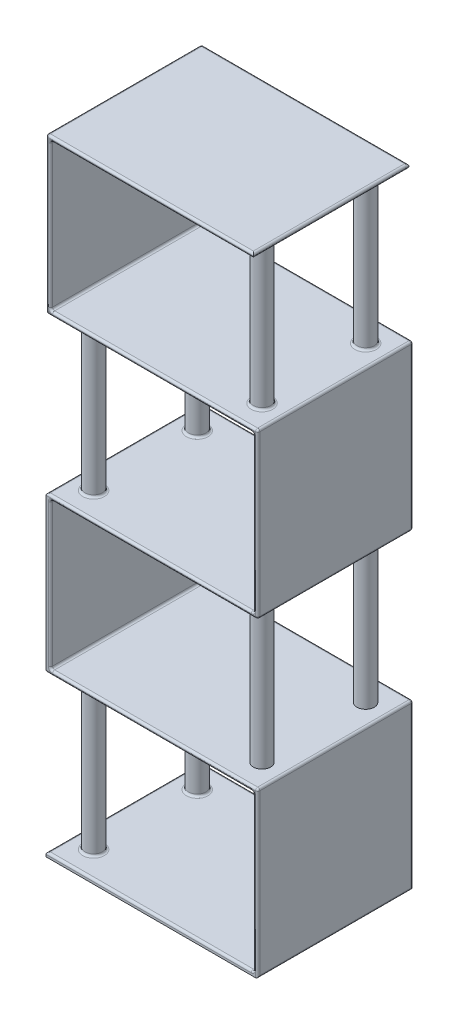
SolidWorks part; units mm, degrees
ref_plane "Front Plane" through (0, 0, 0) normal (0, 0, 1) x (1, 0, 0)
ref_plane "Top Plane" through (0, 0, 0) normal (0, 1, 0) x (1, 0, 0)
ref_plane "Right Plane" through (0, 0, 0) normal (1, 0, 0) x (0, 0, -1)
sketch "Sketch1" plane through (0, 0, 0) normal (0, 0, 1) x (1, 0, 0)
  line L0 (0, 0) -> (609.6, 0)
  line L1 (609.6, 0) -> (609.6, 457.2)
  line L2 (609.6, 457.2) -> (0, 457.2)
  line L3 (0, 457.2) -> (0, 914.4)
  line L4 (0, 914.4) -> (609.6, 914.4)
  line L5 (609.6, 914.4) -> (609.6, 1371.6)
  line L6 (609.6, 1371.6) -> (0, 1371.6)
  line L7 (0, 1371.6) -> (0, 1828.8)
  line L8 (0, 1828.8) -> (609.6, 1828.8)
  line L9 (0, -12.7) -> (622.3, -12.7)
  line L10 (622.3, -12.7) -> (622.3, 469.9)
  line L11 (622.3, 469.9) -> (12.7, 469.9)
  line L12 (12.7, 469.9) -> (12.7, 901.7)
  line L13 (12.7, 901.7) -> (622.3, 901.7)
  line L14 (622.3, 901.7) -> (622.3, 1384.3)
  line L15 (622.3, 1384.3) -> (12.7, 1384.3)
  line L16 (12.7, 1384.3) -> (12.7, 1816.1)
  line L17 (12.7, 1816.1) -> (609.6, 1816.1)
  line L18 (609.6, 1816.1) -> (609.6, 1828.8)
  line L19 (0, -12.7) -> (0, 0)
  dimension "D1" = 609.6
  dimension "D2" = 1828.8
  dimension "D3" = 12.7
extrude "Boss-Extrude1" add sketch "Sketch1" along normal mid plane 457.2
sketch "Sketch2" plane through (0, 0, 0) normal (0, 1, 0) x (1, 0, 0)
  line L0 (0, -228.6) -> (0, 228.6) construction
  circle A0 centre (63.5, 152.4) radius 25.4
  circle A1 centre (63.5, -152.4) radius 25.4
  point P4 (0, 0)
  dimension "D1" = 152.4
  dimension "D4" = 50.8
  dimension "D2" = 152.4
  dimension "D3" = 63.5
extrude "Boss-Extrude2" add sketch "Sketch2" along normal up to next
pattern_linear "LPattern1" count 2 spacing 914.4 along (0, 1, 0) of "Boss-Extrude2"
sketch "Sketch3" plane through (0, 469.9, 0) normal (0, 1, 0) x (1, 0, 0)
  line L0 (622.3, -228.6) -> (622.3, 228.6) construction
  circle A0 centre (558.8, 152.4) radius 25.4
  circle A1 centre (558.8, -152.4) radius 25.4
  point P4 (0, 0)
  dimension "D1" = 152.4
  dimension "D4" = 50.8
  dimension "D2" = 152.4
  dimension "D3" = 63.5
extrude "Boss-Extrude3" add sketch "Sketch3" along normal up to next
pattern_linear "LPattern2" count 2 spacing 914.4 along (0, 1, 0) of "Boss-Extrude3"
fillet "Fillet1" radius 6.35 65 edges at (609.6, 228.6, 228.6) (609.6, 228.6, -228.6) (317.5, 469.9, 228.6) (317.5, 469.9, -228.6) (609.6, 1143, 228.6) (609.6, 1143, -228.6) (12.7, 1600.2, 228.6) (12.7, 1600.2, -228.6) (622.3, -12.7, 0) (622.3, 228.6, 228.6) (622.3, 469.9, 0) (622.3, 228.6, -228.6) (609.6, 0, 0) (304.8, 0, 228.6) (0, 0, 0) (304.8, 0, -228.6) (63.5, 0, -177.8) (63.5, 0, 127) (0, 457.2, 0) (304.8, 457.2, 228.6) (609.6, 457.2, 0) (304.8, 457.2, -228.6) (38.1, 457.2, -152.4) (38.1, 457.2, 152.4) (12.7, 469.9, 0) (12.7, 685.8, 228.6) (12.7, 685.8, -228.6) (12.7, 901.7, 0) (317.5, 901.7, 228.6) (317.5, 901.7, -228.6) (558.8, 901.7, -127) (558.8, 901.7, 177.8) (304.8, 1371.6, 228.6) (609.6, 1371.6, 0) (304.8, 1371.6, -228.6) (38.1, 1371.6, -152.4) (38.1, 1371.6, 152.4) (0, 1600.2, 228.6) (0, 1371.6, 0) (0, 1600.2, -228.6) (622.3, 901.7, 0) (622.3, 1143, 228.6) (622.3, 1143, -228.6) (609.6, 914.4, 0) (304.8, 914.4, 228.6) (0, 914.4, 0) (304.8, 914.4, -228.6) (63.5, 914.4, -177.8) (63.5, 914.4, 127) (622.3, 1384.3, 0) (317.5, 1384.3, 228.6) (12.7, 1384.3, 0) (317.5, 1384.3, -228.6) (584.2, 1384.3, -152.4) (584.2, 1384.3, 152.4) (12.7, 1816.1, 0) (311.15, 1816.1, 228.6) (609.6, 1816.1, 0) (311.15, 1816.1, -228.6) (558.8, 1816.1, -127) (558.8, 1816.1, 177.8) (609.6, 1828.8, 0) (304.8, 1828.8, 228.6) (0, 1828.8, 0) (304.8, 1828.8, -228.6)
